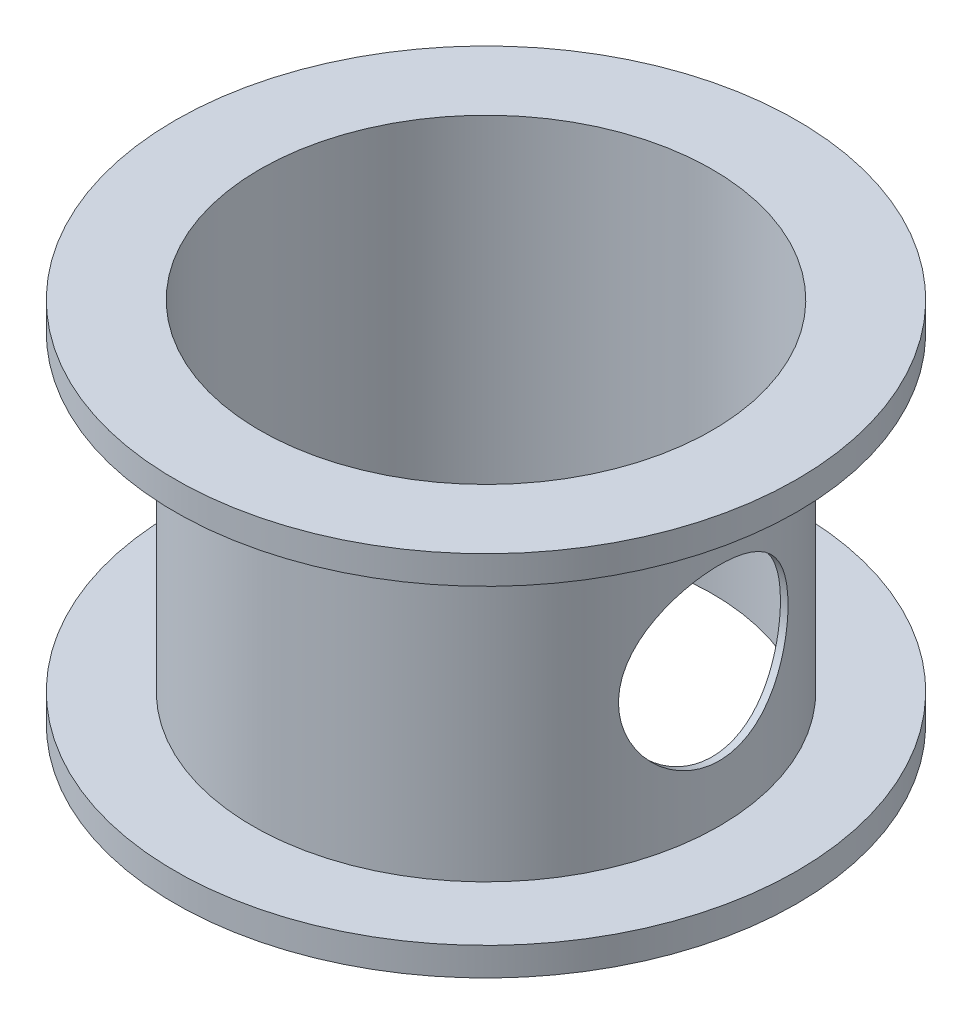
SolidWorks part; units mm, degrees
ref_plane "Front Plane" through (0, 0, 0) normal (0, 0, 1) x (1, 0, 0)
ref_plane "Top Plane" through (0, 0, 0) normal (0, 1, 0) x (1, 0, 0)
ref_plane "Right Plane" through (0, 0, 0) normal (1, 0, 0) x (0, 0, -1)
sketch "Sketch1" plane through (0, 0, 0) normal (0, 0, 1) x (1, 0, 0)
  line L0 (0, 1125.8152) -> (0, -48874.1848) construction
  line L1 (101.6, 1061.593) -> (104.775, 1061.593)
  line L2 (101.6, 1061.593) -> (101.6, 921.893)
  line L3 (101.6, 921.893) -> (104.775, 921.893)
  line L4 (104.775, 1061.593) -> (104.775, 921.893)
  line L5 (101.6, 909.193) -> (139.7, 909.193)
  line L6 (101.6, 909.193) -> (101.6, 921.893)
  line L7 (101.6, 921.893) -> (139.7, 921.893)
  line L8 (139.7, 909.193) -> (139.7, 921.893)
  line L9 (101.6, 1074.293) -> (139.7, 1074.293)
  line L10 (101.6, 1074.293) -> (101.6, 1061.593)
  line L11 (101.6, 1061.593) -> (139.7, 1061.593)
  line L12 (139.7, 1074.293) -> (139.7, 1061.593)
revolve "Revolve1" add sketch "Sketch1" angle 360 about L0 region at (120.65, 1067.943, 0) region at (103.1875, 991.743, 0) region at (120.65, 915.543, 0)
sketch "Sketch2" plane through (0, 0, 0) normal (0, 0, 1) x (1, 0, 0)
  line L0 (65.7096, 1023.493) -> (104.775, 1023.493)
  line L1 (104.775, 1023.493) -> (104.775, 985.393)
  line L2 (180.975, 985.393) -> (0, 985.393) construction
  line L3 (104.775, 985.393) -> (65.7096, 985.393)
  line L4 (65.7096, 985.393) -> (65.7096, 1023.493)
  line L5 (180.975, 985.393) -> (0, 985.393) construction
revolve "Cut-Revolve2" cut sketch "Sketch2" angle 360 about L5
sketch "Sketch4" plane through (0, 909.193, 0) normal (0, -1, 0) x (1, 0, 0)
  line L0 (0, 0) -> (58.7375, 101.7363) construction
  line L1 (0, 0) -> (58.7375, -101.7363) construction
  line L2 (0, 0) -> (-117.475, 0) construction
  circle A0 centre (0, 0) radius 117.475 construction
  circle A1 centre (0, 0) radius 123.825
  circle A2 centre (0, 0) radius 111.125
  dimension "D1" = 120
  dimension "D2" = 120
  dimension "D3" = 6.35
  dimension "D4" = 6.35
